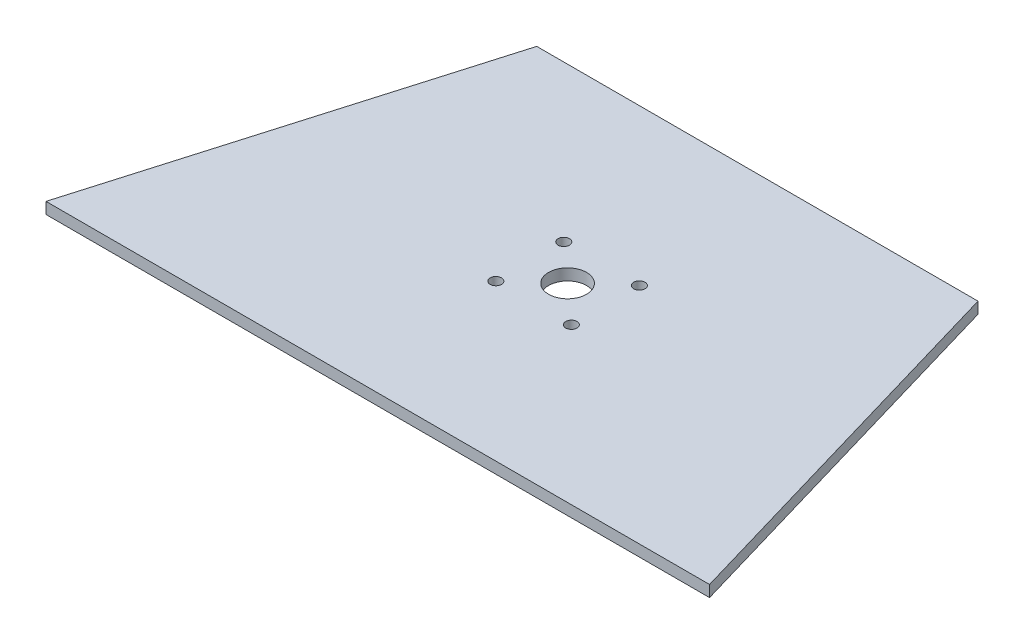
SolidWorks part; units mm, degrees
ref_plane "Front Plane" through (0, 0, 0) normal (0, 0, 1) x (1, 0, 0)
ref_plane "Top Plane" through (0, 0, 0) normal (0, 1, 0) x (1, 0, 0)
ref_plane "Right Plane" through (0, 0, 0) normal (1, 0, 0) x (0, 0, -1)
sketch "Sketch1" plane through (0, 0, 0) normal (0, 1, 0) x (1, 0, 0)
  line L0 (5.2, 0) -> (180, 0)
  line L3 (90, 0) -> (90, 100) construction
  line L5 (5.2, 0) -> (34.4799, 100)
  line L6 (180, 0) -> (150.7201, 100)
  line L7 (34.4799, 100) -> (150.7201, 100)
extrude "Boss-Extrude1" add sketch "Sketch1" along normal blind 3
hole_wizard "Ø3.0mm Dowel Hole1" positions "Sketch2" profile "Sketch3" hole size "Ø3.0" standard "ANSI Metric" end condition up to next
sketch "Sketch2" plane through (0, 0, 0) normal (0, -1, 0) x (-1, 0, 0)
  point P0 (-82.65, 58.95)
  point P3 (-82.65, 41.05)
  point P6 (-102.55, 41.05)
  point P9 (-102.55, 58.95)
  point P13 (0, 0)
  point P14 (0, 0)
  point P15 (0, 0)
  point P16 (0, 0)
sketch "Sketch3" plane through (82.65, 0, -58.95) normal (1, 0, 0) x (0, 0, -1)
  line L0 (0, 0) -> (0, 3)
  line L1 (0, 3) -> (1.5, 3)
  line L2 (1.5, 3) -> (1.5, 0)
  line L5 (1.5, 0) -> (0, 0)
  line L11 (0, -6.35) -> (0, 107.95) construction
  dimension "Thru Hole Dia." = 3
  dimension "Thru Hole Depth" = 3
hole_wizard "Ø10.0mm Dowel Hole1" positions "Sketch6" profile "Sketch7" hole size "Ø10.0" standard "ANSI Metric" end condition up to next
sketch "Sketch6" plane through (0, 3, 0) normal (0, 1, 0) x (1, 0, 0)
  point P0 (92.6, 50)
  point P4 (0, 0)
sketch "Sketch7" plane through (92.6, 3, -50) normal (1, 0, 0) x (0, 0, 1)
  line L0 (0, 0) -> (0, 3)
  line L1 (0, 3) -> (5, 3)
  line L2 (5, 3) -> (5, 0)
  line L5 (5, 0) -> (0, 0)
  line L11 (0, -6.35) -> (0, 107.95) construction
  dimension "Thru Hole Dia." = 10
  dimension "Thru Hole Depth" = 3
